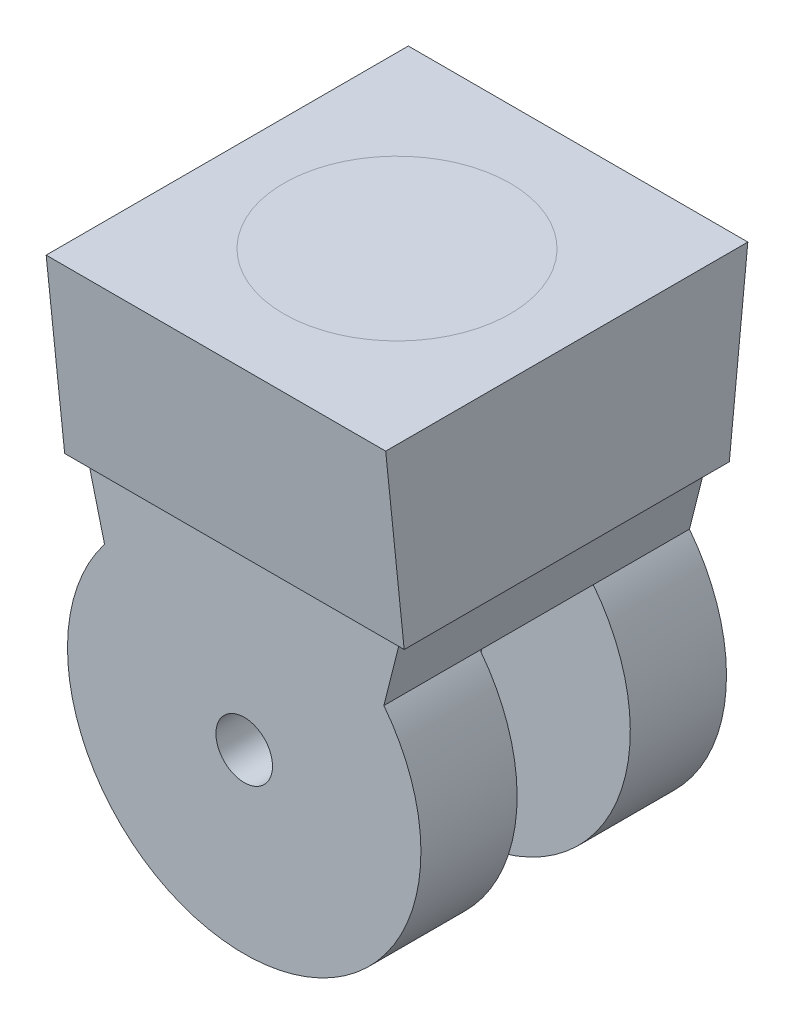
SolidWorks part; units mm, degrees
ref_plane "Alzado" through (0, 0, 0) normal (0, 0, 1) x (1, 0, 0)
ref_plane "Planta" through (0, 0, 0) normal (0, 1, 0) x (1, 0, 0)
ref_plane "Vista lateral" through (0, 0, 0) normal (1, 0, 0) x (0, 0, -1)
sketch "Croquis1" plane through (0, 0, 0) normal (1, 0, 0) x (0, 0, -1)
  line L0 (-40.64, 20.32) -> (-36.4861, -20.32)
  line L1 (-36.4861, -20.32) -> (0, -20.32)
  line L2 (40.64, 20.32) -> (36.4861, -20.32)
  line L3 (36.4861, -20.32) -> (0, -20.32)
  line L4 (-40.64, 20.32) -> (40.64, 20.32)
extrude "Saliente-Extruir1" add sketch "Croquis1" along normal mid plane 76.2
sketch "Croquis2" plane through (0, 0, 0) normal (0, 0, 1) x (1, 0, 0)
  line L0 (35.2237, -20.32) -> (31.3489, -35.6876)
  line L1 (38.1, -20.32) -> (-38.1, -20.32) construction
  line L2 (0, 34.8542) -> (0, -59.9788) construction
  line L3 (-35.2237, -20.32) -> (35.2237, -20.32)
  line L4 (-35.2237, -20.32) -> (-31.3489, -35.6876)
  arc A0 (-31.3489, -35.6876) -> (31.3489, -35.6876) centre (0, -59.9788) ccw
extrude "Saliente-Extruir2" add sketch "Croquis2" along normal mid plane 68.58
sketch "Croquis3" plane through (0, 0, 0) normal (0, 0, 1) x (1, 0, 0)
  circle A0 centre (0, -59.9788) radius 39.6588
  dimension "D1" = 79.3175
extrude "Cortar-Extruir1" cut sketch "Croquis3" against normal mid plane 25.4
sketch "Croquis4" plane through (0, 0, 34.29) normal (0, 0, 1) x (1, 0, 0)
  circle A0 centre (0, -59.9788) radius 6.35
  dimension "D1" = 12.7
extrude "Cortar-Extruir2" cut sketch "Croquis4" against normal through all
sketch "Croquis8" plane through (0, 20.32, 0) normal (0, 1, 0) x (1, 0, 0)
  circle A0 centre (0, 0) radius 25.4
  dimension "D1" = 50.8
split line "Línea de partición1"
ref_point "Point1"
ref_axis "Axis1" through (0, 20.32, 0) along (0, 1, 0)
